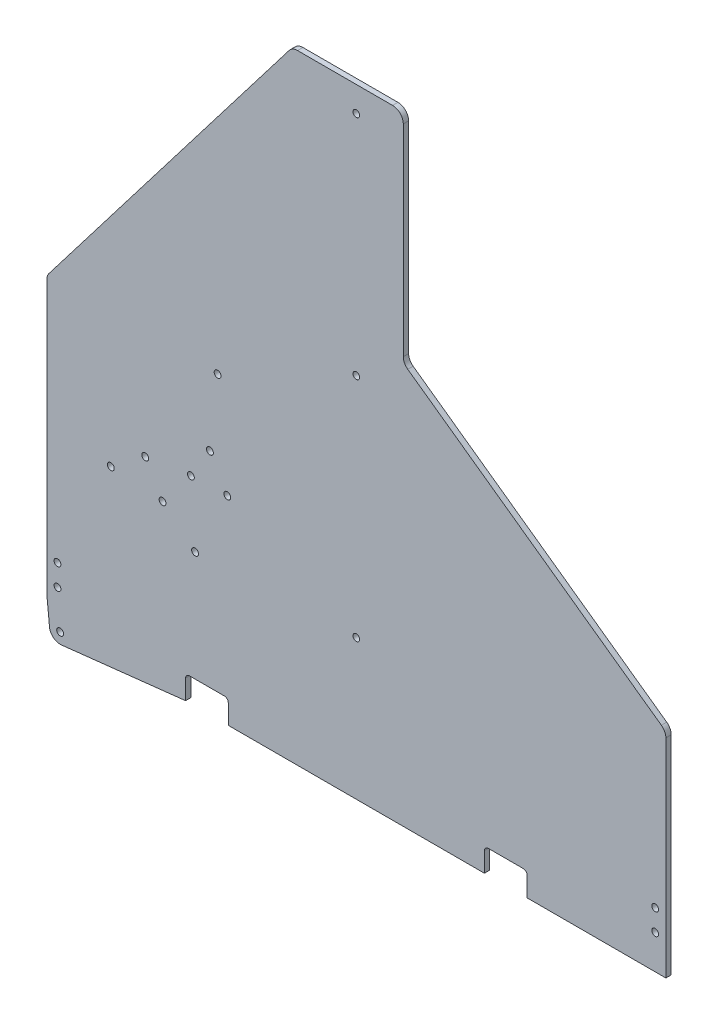
SolidWorks part; units mm, degrees
ref_plane "Front Plane" through (0, 0, 0) normal (0, 0, 1) x (1, 0, 0)
ref_plane "Top Plane" through (0, 0, 0) normal (0, 1, 0) x (1, 0, 0)
ref_plane "Right Plane" through (0, 0, 0) normal (1, 0, 0) x (0, 0, -1)
sketch "Sketch1" plane through (0, 0, 0) normal (0, 0, 1) x (1, 0, 0)
  line L0 (82.55, -20.32) -> (82.55, -6.35)
  line L2 (0, 0) -> (0, 157.48)
  line L4 (368.3, -20.32) -> (368.3, 106.68)
  line L5 (82.55, -6.35) -> (107.95, -6.35)
  line L6 (107.95, -6.35) -> (107.95, -20.32)
  line L7 (107.95, -20.32) -> (260.35, -20.32)
  line L8 (260.35, -20.32) -> (260.35, -6.35)
  line L9 (260.35, -6.35) -> (285.75, -6.35)
  line L10 (285.75, -6.35) -> (285.75, -20.32)
  line L11 (285.75, -20.32) -> (368.3, -20.32)
  line L12 (361.95, 12.7) -> (368.3, 12.7) construction
  line L13 (0, 0) -> (6.35, 0) construction
  line L14 (0.0315, -6.9818) -> (1.619, -22.8568)
  line L15 (8.6391, -28.5361) -> (82.55, -20.32)
  line L16 (0, 0) -> (0, -6.35)
  line L17 (85.725, 97.155) -> (82.9754, 95.5675) construction
  line L18 (97.0634, 115.6163) -> (58.5686, 93.3913) construction
  line L19 (97.0634, 115.6163) -> (107.3822, 97.7437) construction
  line L20 (58.5686, 93.3913) -> (68.8873, 75.5187) construction
  line L21 (107.3822, 97.7437) -> (68.8873, 75.5187) construction
  line L22 (97.0634, 115.6163) -> (68.8873, 75.5187) construction
  line L23 (58.5686, 93.3913) -> (107.3822, 97.7437) construction
  line L24 (7.9375, -22.225) -> (88.2169, 59.1366) construction
  line L25 (184.15, 62.98) -> (184.15, 197.98) construction
  line L26 (184.15, 197.98) -> (184.15, 332.98) construction
  line L27 (355.6, 335.28) -> (330.2, 335.28) construction
  line L28 (330.2, 335.28) -> (330.2, 220.98) construction
  line L29 (330.2, 220.98) -> (355.6, 220.98) construction
  line L30 (355.6, 220.98) -> (355.6, 335.28) construction
  line L31 (184.15, 347.98) -> (184.15, 269.4703) construction
  line L32 (12.7, 335.28) -> (38.1, 335.28) construction
  line L33 (38.1, 335.28) -> (38.1, 220.98) construction
  line L34 (12.7, 220.98) -> (12.7, 335.28) construction
  line L35 (38.1, 220.98) -> (12.7, 220.98) construction
  line L36 (146.05, 347.98) -> (184.15, 347.98)
  line L37 (184.15, 347.98) -> (146.05, 347.98)
  line L38 (184.15, 347.98) -> (212.09, 347.98)
  line L39 (348.5362, 347.98) -> (413.4623, 347.98)
  line L40 (348.5362, 347.98) -> (-141.0713, 347.98) construction
  line L42 (146.05, 347.98) -> (0, 157.48)
  line L44 (212.09, 347.98) -> (212.09, 218.44)
  line L45 (212.09, 218.44) -> (368.3, 106.68)
  circle A0 centre (6.35, 0) radius 2.032
  circle A1 centre (6.35, 12.7) radius 2.032
  circle A2 centre (361.95, 0) radius 2.032
  circle A3 centre (361.95, 12.7) radius 2.032
  arc A5 (1.619, -22.8568) -> (8.6391, -28.5361) centre (7.9375, -22.225) ccw
  circle A6 centre (7.9375, -22.225) radius 2.032
  arc A7 (0, -6.35) -> (0.0315, -6.9818) centre (6.35, -6.35) ccw
  circle A8 centre (38.1, 78.105) radius 2.032
  circle A9 centre (85.725, 97.155) radius 2.032
  circle A10 centre (58.5686, 93.3913) radius 2.032
  circle A11 centre (68.8873, 75.5187) radius 2.032
  circle A12 centre (107.3822, 97.7437) radius 2.032
  circle A13 centre (97.0634, 115.6163) radius 2.032
  circle A14 centre (88.2169, 59.1366) radius 2.032
  circle A15 centre (184.15, 62.98) radius 2
  circle A16 centre (184.15, 197.98) radius 2
  circle A17 centre (184.15, 332.98) radius 2
  circle A18 centre (63.5, 316.23) radius 2.032
  circle A19 centre (101.6, 157.48) radius 2.032
  circle A20 centre (355.6, 335.28) radius 2.032
  circle A21 centre (330.2, 335.28) radius 2.032
  circle A22 centre (355.6, 220.98) radius 2.032
  circle A23 centre (330.2, 220.98) radius 2.032
  circle A24 centre (12.7, 335.28) radius 2.032
  circle A25 centre (38.1, 335.28) radius 2.032
  circle A26 centre (12.7, 220.98) radius 2.032
  circle A27 centre (38.1, 220.98) radius 2.032
  point P82 (184.15, 347.98)
  dimension "D6" = 4.064
  dimension "D10" = 6.35
  dimension "D11" = 4.064
  dimension "D17" = 38.1
  dimension "D27" = 4
  dimension "D31" = 4.064
  dimension "D32" = 38.1
  dimension "D36" = 4.064
  dimension "D2" = 127
  dimension "D3" = 13.97
  dimension "D4" = 25.4
  dimension "D5" = 152.4
  dimension "D7" = 12.7
  dimension "D8" = 6.35
  dimension "D9" = 20.32
  dimension "D12" = 22.225
  dimension "D13" = 1.5875
  dimension "D14" = 82.55
  dimension "D15" = 368.3
  dimension "D16" = 6.35
  dimension "D18" = 98.425
  dimension "D19" = 47.625
  dimension "D20" = 19.05
  dimension "D21" = 3.175
  dimension "D22" = 60
  dimension "D23" = 20.6375
  dimension "D24" = 44.45
  dimension "D25" = 38.1
  dimension "D26" = 114.3
  dimension "D28" = 135
  dimension "D29" = 12.7
  dimension "D30" = 15
  dimension "D33" = 63.5
  dimension "D34" = 27.94
  dimension "D35" = 101.6
  dimension "D37" = 114.3
  dimension "D38" = 25.4
  dimension "D39" = 12.7
  dimension "D40" = 157.48
  dimension "D41" = 129.54
  dimension "D42" = 368.3
extrude "Boss-Extrude1" add sketch "Sketch1" along normal blind 3.175 contours L16 A7 L14 A5 L15 L0 L5 L6 L7 L8 L9 L10 L11 L4 L42 L2 A19 A17 A16 A15 A14 A13 A12 A11 A10 A9 A8 A0 A1 A2 A3 A6 region at (168.3767, 118.6221, 0)
fillet "Fillet1" radius 2.286 4 edges at (285.75, -6.35, 1.5875) (107.95, -6.35, 1.5875) (260.35, -6.35, 1.5875) (82.55, -6.35, 1.5875)
fillet "Fillet2" radius 6.35 5 edges at (0, 157.48, 1.5875) (212.09, 347.98, 1.5875) (212.09, 218.44, 1.5875) (368.3, 106.68, 1.5875) (146.05, 347.98, 1.5875)
